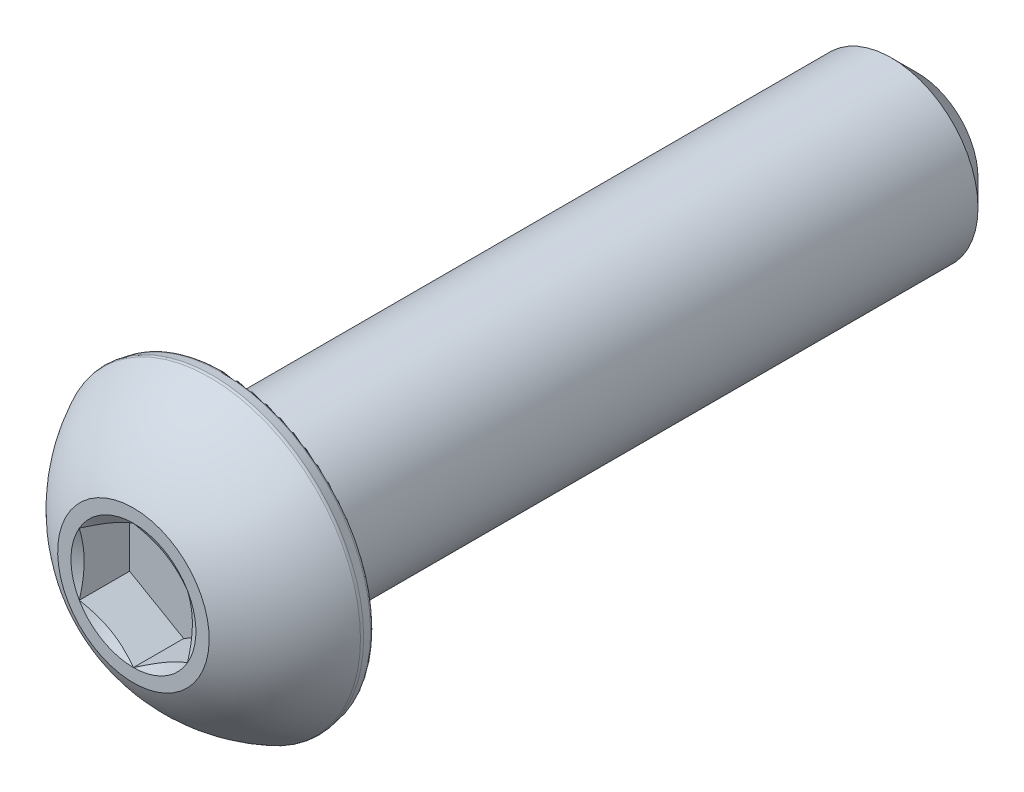
SolidWorks part; units mm, degrees
ref_plane "Front Plane" through (0, 0, 0) normal (0, 0, 1) x (1, 0, 0)
ref_plane "Top Plane" through (0, 0, 0) normal (0, 1, 0) x (1, 0, 0)
ref_plane "Right Plane" through (0, 0, 0) normal (1, 0, 0) x (0, 0, -1)
sketch "Sketch1" plane through (0, 0, 0) normal (1, 0, 0) x (0, 0, -1)
  line L0 (-14.3764, 0) -> (14.3764, 0) construction
  line L1 (-14.3764, 0) -> (-14.3764, 5.5499)
  line L2 (-14.3764, 5.5499) -> (-11.0236, 5.5499)
  line L3 (-11.0236, 5.5499) -> (-11.0236, 3.175)
  line L4 (-11.0236, 3.175) -> (14.3764, 3.175)
  line L5 (14.3764, 3.175) -> (14.3764, 0)
  point P2 (0, 0)
  point P4 (13.1064, 0)
  point P9 (12.4714, 3.175)
  point P10 (12.4714, -3.175)
  point P11 (14.3764, -3.175)
  point P15 (-12.5324, 0)
  dimension "Head Height" = 3.3528
  dimension "Head Diameter" = 11.0998
  dimension "Length" = 25.4
  dimension "Screw Size Decimal Equivalent" = 6.35
  dimension "Thread Pitch" = 1.27
  dimension "D1" = 1.905
  dimension "D2" = 1.844
sketch "Sketch2" plane through (0, 0, 0) normal (0, 0, 1) x (1, 0, 0)
  line L0 (0, 3.175) -> (0, 0) construction
  line L1 (0, 2.2914) -> (-1.9844, 1.1457)
  line L2 (-1.9844, 1.1457) -> (-1.9844, -1.1457)
  line L3 (-1.9844, -1.1457) -> (0, -2.2914)
  line L4 (0, -2.2914) -> (1.9844, -1.1457)
  line L5 (1.9844, -1.1457) -> (1.9844, 1.1457)
  line L6 (1.9844, 1.1457) -> (0, 2.2914)
  circle A0 centre (0, 0) radius 1.9844 construction
  circle A1 centre (0, 0) radius 2.7781
  point P10 (0, 2.7781)
  dimension "D1" = 5.5563
  dimension "Drive Size" = 3.9688
sketch "Sketch3" plane through (0, 0, 0) normal (1, 0, 0) x (0, 0, -1)
  line L0 (-14.3764, 0) -> (-14.3764, 2.7781)
  line L1 (-14.3764, 0) -> (-14.3764, 5.5499) construction
  line L2 (-14.3764, 5.5499) -> (-11.0236, 5.5499) construction
  line L3 (-11.5265, 5.5499) -> (-11.0236, 5.4612)
  line L4 (-11.0236, 5.5499) -> (-11.0236, 3.175) construction
  line L5 (-11.0236, 5.4612) -> (-11.0236, 3.175)
  line L6 (-14.3764, 0) -> (14.3764, 0) construction
  line L7 (-14.3764, 0) -> (14.3764, 0)
  line L8 (14.3764, 0) -> (14.3764, 2.2225)
  line L9 (14.3764, 3.175) -> (14.3764, 0) construction
  line L10 (14.3764, 2.2225) -> (13.4239, 3.175)
  line L11 (-11.0236, 3.175) -> (14.3764, 3.175) construction
  line L12 (13.4239, 3.175) -> (-11.0236, 3.175)
  arc A0 (-14.3764, 2.7781) -> (-11.5265, 5.5499) centre (-8.9016, 0) cw
  dimension "D1" = 0.5029
  dimension "D2" = 10
  dimension "D3" = 45
  dimension "D4" = 0.9525
revolve "Revolve1" add sketch "Sketch3" angle 360 about L7
sketch "Sketch4" plane through (0, 0, 14.3764) normal (0, 0, 1) x (1, 0, 0)
  line L0 (-1.9844, -1.1457) -> (0, -2.2914) construction
  line L1 (-1.9844, 1.1457) -> (-1.9844, -1.1457) construction
  line L2 (0, 2.2914) -> (-1.9844, 1.1457) construction
  line L3 (1.9844, 1.1457) -> (0, 2.2914) construction
  line L4 (1.9844, -1.1457) -> (1.9844, 1.1457) construction
  line L5 (0, -2.2914) -> (1.9844, -1.1457) construction
  line L6 (-1.9844, -1.1457) -> (0, -2.2914)
  line L7 (-1.9844, 1.1457) -> (-1.9844, -1.1457)
  line L8 (0, 2.2914) -> (-1.9844, 1.1457)
  line L9 (1.9844, 1.1457) -> (0, 2.2914)
  line L10 (1.9844, -1.1457) -> (1.9844, 1.1457)
  line L11 (0, -2.2914) -> (1.9844, -1.1457)
extrude "Cut-Extrude1" cut sketch "Sketch4" against normal up to vertex (1.844 mm away) up to point (0, 0, 12.5324)
sketch "Sketch5" plane through (0, 0, 14.3764) normal (0, 0, 1) x (1, 0, 0)
  circle A0 centre (0, 0) radius 2.2914
extrude "Cut-Extrude2" cut sketch "Sketch5" against normal up to vertex (1.844 mm away) draft 60 up to point (0, 0, 12.5324)
fillet "Fillet1" radius 0.1676 2 edges at (5.5499, 0, 11.5265) (5.4612, 0, 11.0236)
split "Split1" [suppressed] bodies to split 106
sketch "Sketch6" [suppressed] plane through (0, 0, -14.3764) normal (0, 0, -1) x (-1, 0, 0)
  circle A0 centre (0, 0) radius 3.175 construction
  circle A1 centre (0, 0) radius 3.175
curve "Helix/Spiral1" [suppressed] pitch 1.27 height 26.67 turns 21
sketch "Sketch7" [suppressed] plane through (0, 0, 0) normal (1, 0, 0) x (0, 0, -1)
  line L0 (14.297, 3.3125) -> (14.932, 2.2126) construction
  line L1 (14.932, 2.2126) -> (15.567, 3.3125) construction
  line L2 (15.567, 3.3125) -> (14.297, 3.3125) construction
  line L3 (14.3367, 3.2437) -> (15.5273, 3.2437)
  line L4 (15.5273, 3.2437) -> (15.0114, 2.3501)
  line L5 (15.0114, 2.3501) -> (14.8527, 2.3501)
  line L6 (14.8527, 2.3501) -> (14.3367, 3.2437)
  line L7 (14.932, 2.3501) -> (14.932, 2.2126) construction
  line L8 (14.3764, 3.175) -> (15.4877, 3.175) construction
  line L9 (14.932, 3.3125) -> (14.932, 3.175) construction
  point P12 (14.932, 3.2437)
  dimension "D1" = 1.27
  dimension "D2" = 0.1588
sweep "Cut-Sweep1" [suppressed] cut profiles "Sketch7" path "Helix/Spiral1"
sketch "Sketch8" [suppressed] plane through (0, 0, 11.0236) normal (0, 0, -1) x (-1, 0, 0)
  circle A0 centre (0, 0) radius 3.3125
extrude "Boss-Extrude1" [suppressed] add sketch "Sketch8" along normal up to vertex draft 45 up to point (0, 3.175, -12.4714)
equation "\"D1@Sketch1\"=\"Thread Pitch@Sketch1\"*1.5"
equation "\"D2@Sketch1\"=0.55*\"Head Height@Sketch1\""
equation "\"D1@Sketch2\"=\"Drive Size@Sketch2\"*1.4"
equation "\"D1@Sketch3\"=0.15*\"Head Height@Sketch1\""
equation "\"D4@Sketch3\"=0.75*\"Thread Pitch@Sketch1\""
equation "\"D1@Fillet1\"=.05*\"Head Height@Sketch1\""
equation "\"D4@Helix/Spiral1\"=\"Thread Pitch@Sketch1\""
equation "\"D3@Helix/Spiral1\"=\"Length@Sketch1\"+\"Thread Pitch@Sketch1\""
equation "\"D2@Sketch7\"=\"D1@Sketch7\"/8"
equation "\"D1@Sketch7\"=\"Thread Pitch@Sketch1\""
